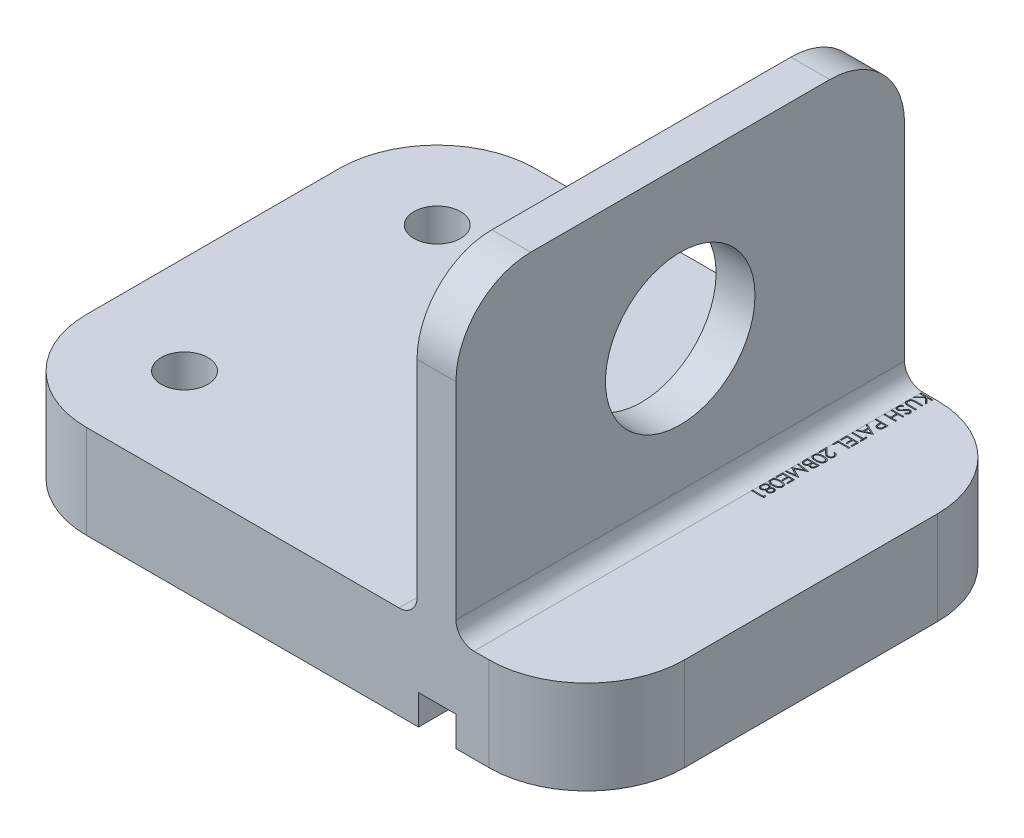
SolidWorks part; units mm, degrees
ref_plane "Front Plane" through (0, 0, 0) normal (0, 0, 1) x (1, 0, 0)
ref_plane "Top Plane" through (0, 0, 0) normal (0, 1, 0) x (1, 0, 0)
ref_plane "Right Plane" through (0, 0, 0) normal (1, 0, 0) x (0, 0, -1)
sketch "Sketch1" plane through (0, 0, 0) normal (0, 1, 0) x (1, 0, 0)
  line L1 (0, 0) -> (4000, 0)
  line L2 (0, 0) -> (0, 3000)
  line L3 (0, 3000) -> (4000, 3000)
  line L4 (4000, 0) -> (4000, 3000)
  line L5 (2865, 3000) -> (3125, 3000)
  line L6 (2865, 3000) -> (2865, 0)
  line L7 (2865, 0) -> (3125, 0)
  line L8 (3125, 3000) -> (3125, 0)
  circle A0 centre (655, 2345) radius 156
  circle A1 centre (655, 655) radius 156
  dimension "D7" = 260
  dimension "D1" = 4000
  dimension "D2" = 3000
  dimension "D3" = 655
  dimension "D4" = 655
  dimension "D5" = 2345
  dimension "D6" = 2345
  dimension "D8" = 875
extrude "Boss-Extrude2" add sketch "Sketch1" along normal blind 625 contours L6 L3 L2 L1 A1 A0 | L3 L8 L1 L4 region at (1446.5825, 0, -1500) region at (3562.5, 0, -1500)
extrude "Boss-Extrude3" add sketch "Sketch1<4>" along normal blind 2625 contours L8 L3 L6 L1 region at (2995, 0, -1500)
sketch "Sketch1<4>" plane through (0, 0, 0) normal (0, 1, 0) x (1, 0, 0) same geometry as "Sketch1"
sketch "Sketch2" plane through (3125, 0, 0) normal (1, 0, 0) x (0, 0, -1)
  line L0 (0, 2625) -> (0, 625) construction
  line L1 (3000, 2625) -> (0, 2625) construction
  circle A0 centre (1500, 1625) radius 500
  dimension "D1" = 1000
  dimension "D2" = 1500
  dimension "D3" = 1000
extrude "Cut-Extrude1" cut sketch "Sketch2" against normal blind 1000 contours A0
sketch "Sketch3" plane through (0, 0, 0) normal (0, -1, 0) x (1, 0, 0)
  line L0 (0, 0) -> (4000, 0) construction
  line L1 (2875, 0) -> (3125, 0)
  line L2 (2875, 0) -> (2875, -3000)
  line L3 (2875, -3000) -> (3125, -3000)
  line L4 (3125, 0) -> (3125, -3000)
  line L5 (0, -3000) -> (4000, -3000) construction
  dimension "D1" = 250
  dimension "D2" = 875
extrude "Cut-Extrude2" cut sketch "Sketch3" against normal blind 200 contours L2 L1 L4 L3
fillet "Fillet2" radius 655 1 edges at (0, 312.5, 0)
fillet "Fillet3" radius 655 1 edges at (0, 312.5, -3000)
fillet "Fillet4" radius 655 1 edges at (4000, 312.5, 0)
fillet "Fillet5" radius 655 1 edges at (4000, 312.5, -3000)
fillet "Fillet11" radius 120 1 edges at (2865, 625, -1500)
fillet "Fillet13" radius 120 1 edges at (3125, 625, -1500)
fillet "Fillet14" radius 500 1 edges at (2995, 2625, 0)
fillet "Fillet15" radius 500 1 edges at (2995, 2625, -3000)
sketch "Sketch6" plane through (0, 625, 0) normal (0, 1, 0) x (1, 0, 0)
  text T0 "KUSH PATEL 20BME081" font "Century Gothic" height 80
extrude "Cut-Extrude4" cut sketch "Sketch6" against normal blind 30
